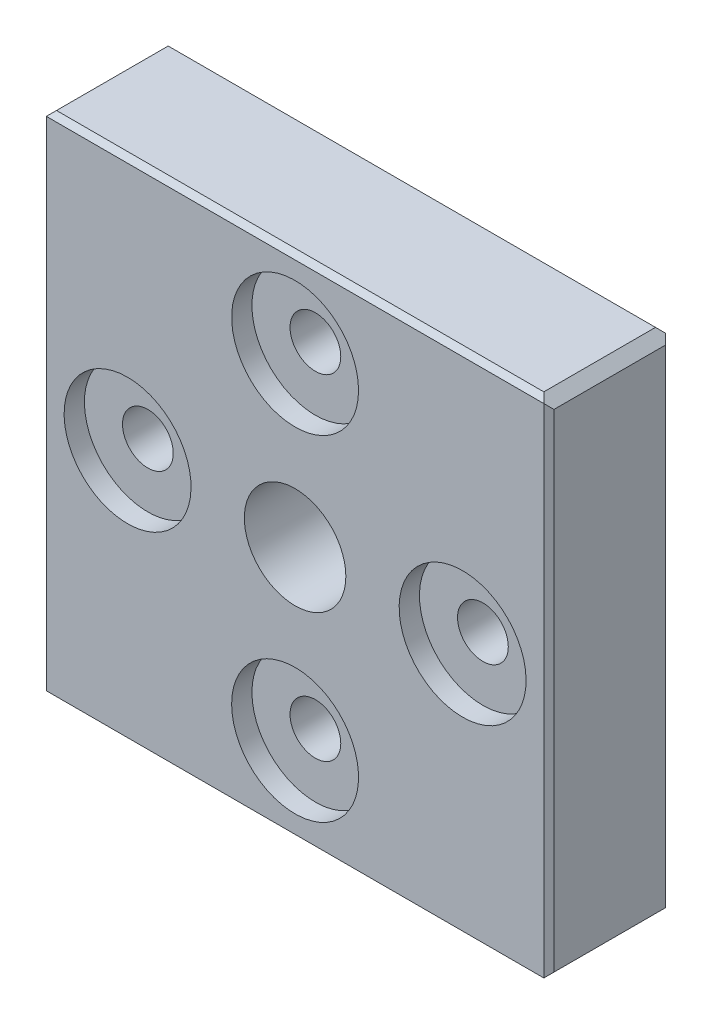
SolidWorks part; units mm, degrees
material "Plain Carbon Steel"
ref_plane "Front Plane" through (0, 0, 0) normal (0, 0, 1) x (1, 0, 0)
ref_plane "Top Plane" through (0, 0, 0) normal (0, 1, 0) x (1, 0, 0)
ref_plane "Right Plane" through (0, 0, 0) normal (1, 0, 0) x (0, 0, -1)
sketch "Sketch1" plane through (0, 0, 0) normal (0, 0, 1) x (1, 0, 0)
  line L1 (-25, -25) -> (25, -25)
  line L2 (-25, -25) -> (-25, 25)
  line L3 (-25, 25) -> (25, 25)
  line L4 (25, -25) -> (25, 25)
  line L5 (-25, -25) -> (25, 25) construction
  line L6 (-25, 25) -> (25, -25) construction
  point P0 (0, 0)
  dimension "D1" = 50
  dimension "D2" = 50
extrude "Boss-Extrude1" add sketch "Sketch1" along normal mid plane 12
sketch "Sketch5" plane through (0, 0, 6) normal (0, 0, 1) x (1, 0, 0)
  circle A0 centre (0, 0) radius 5
  dimension "D1" = 10
extrude "Cut-Extrude1" cut sketch "Sketch5" against normal up to next
chamfer "Chamfer1" distance 1 angle 45 4 edges at (25, -25, 0) (-25, -25, 0) (-25, 25, 0) (25, 25, 0)
chamfer "Chamfer2" distance 0.5 angle 45 8 edges at (0, -25, 6) (0, -25, -6) (0, 25, -6) (0, 25, 6) (25, 0, -6) (25, 0, 6) (-25, 0, -6) (-25, 0, 6)
hole_wizard "M6 Tapped Hole1" positions "Sketch11" profile "Sketch8" tap size "M6" standard "ISO" end condition through all
sketch "Sketch11" plane through (0, 0, 6) normal (0, 0, 1) x (1, 0, 0)
  circle A0 centre (0, 0) radius 16.5 construction
  point P0 (-16.5, 0)
  point P2 (0, 16.5)
  point P4 (16.5, 0)
  point P6 (0, -16.5)
  dimension "D1" = 33
sketch "Sketch8" plane through (-16.5, 0, 6) normal (1, 0, 0) x (0, -1, 0)
  line L0 (0, 0) -> (0, 12)
  line L1 (0, 12) -> (2.5, 12)
  line L2 (2.5, 12) -> (2.5, 0)
  line L5 (2.5, 0) -> (0, 0)
  line L11 (0, -6.35) -> (0, 107.95) construction
  dimension "Thru Tap Drill Dia." = 5
  dimension "Thru Tap Drill Depth" = 12
sketch "Sketch10" plane through (0, 0, 6) normal (0, 0, 1) x (1, 0, 0)
  circle A0 centre (0, 16.5) radius 6.25
  dimension "D1" = 12.5
extrude "Cut-Extrude2" cut sketch "Sketch10" against normal blind 2
pattern_circular "CirPattern1" count 4 over 360 about axis through (0, 0, 6) along (0, 0, 1) of "Cut-Extrude2"
